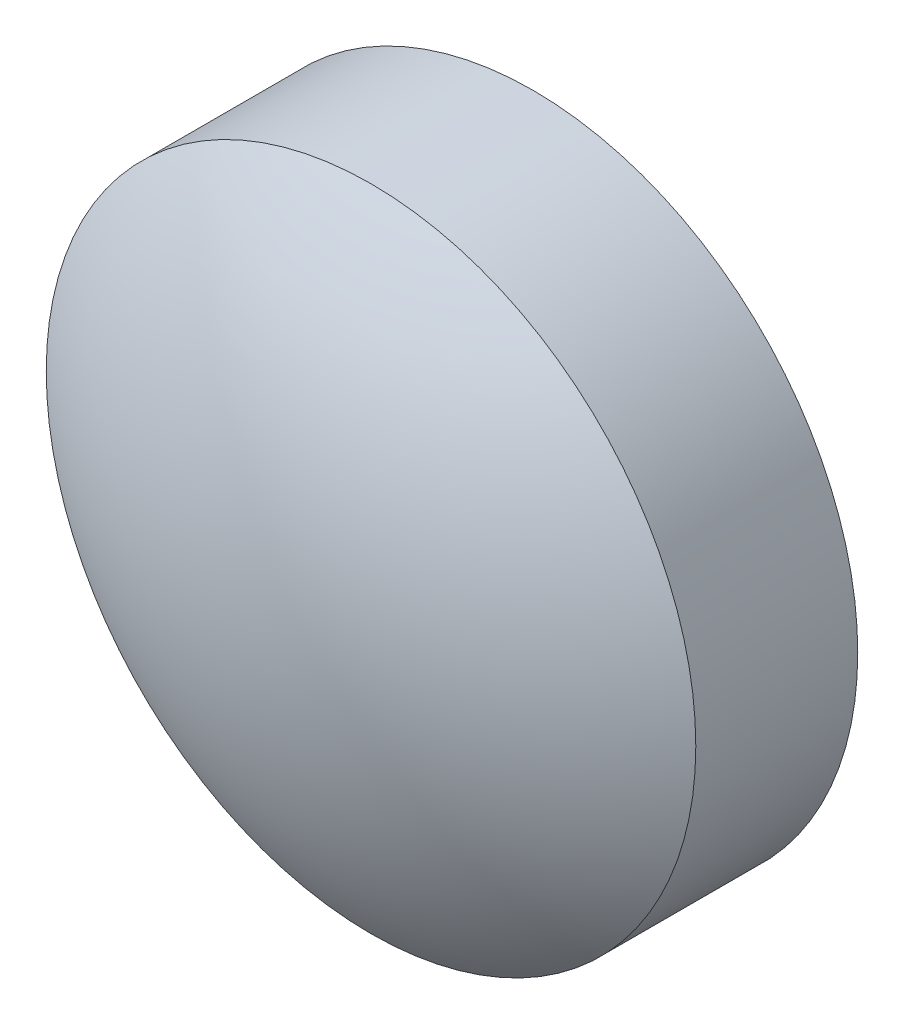
SolidWorks part; units mm, degrees
ref_plane "Ebene vorne" through (0, 0, 0) normal (0, 0, 1) x (1, 0, 0)
ref_plane "Ebene oben" through (0, 0, 0) normal (0, 1, 0) x (1, 0, 0)
ref_plane "Ebene rechts" through (0, 0, 0) normal (1, 0, 0) x (0, 0, -1)
sketch "Skizze1" plane through (0, 0, 0) normal (0, 1, 0) x (1, 0, 0)
  line L0 (3, 1.23) -> (0, 1.23)
  line L1 (0, 1.23) -> (0, -1.23)
  line L2 (3, -0.266) -> (3, 1.23)
  line L3 (0, 1.23) -> (0, -1.23) construction
  arc A0 (0, -1.23) -> (3, -0.266) centre (0, 3.92) ccw
revolve "Rotation1" add sketch "Skizze1" angle 360 about L3 reverse direction yes
ref_axis "SWASI_Optical_Axis" through (0, 0, -1.23) along (0, 0, 1)
ref_plane "Ebene1" through (3, 0, 0) normal (1, 0, 0) x (0, 0, -1)
ref_plane "Ebene2" through (0, 0, -1.23) normal (0, 0, -1) x (-1, 0, 0)
ref_plane "Ebene3" through (0, 0, 0.266) normal (0, 0, 1) x (1, 0, 0)
ref_plane "Ebene4" through (0, 0, -0.482) normal (0, 0, 1) x (1, 0, 0)
ref_axis "Achse3" through (-3.3, 0, -0.482) along (1, 0, 0)
ref_point "Punkt2"
ref_plane "Ebene5" through (-3, 0, 0) normal (-1, 0, 0) x (0, 0, 1)
ref_point "Punkt3"
